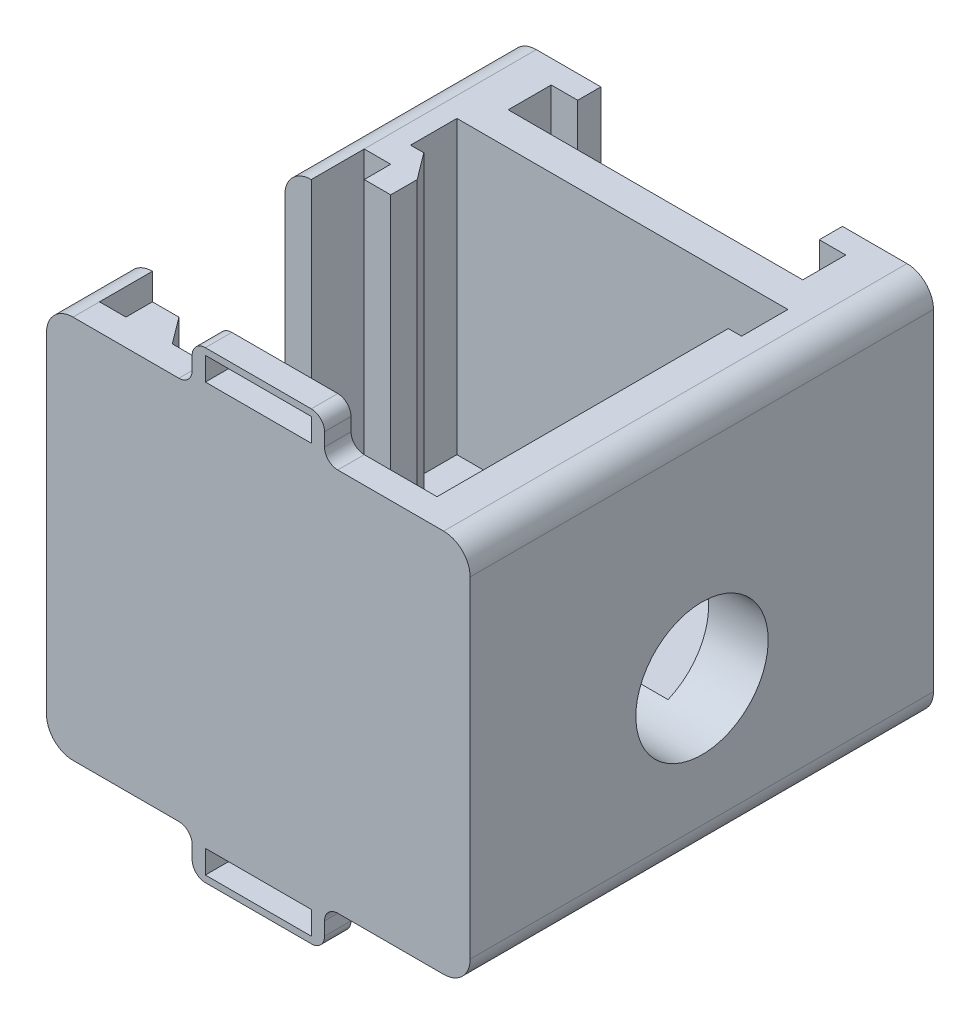
SolidWorks part; units mm, degrees
material "UNOBTANIUM"
ref_plane "Top Plane" through (0, 0, 0) normal (0, 0, 1) x (1, 0, 0)
ref_plane "Right Plane" through (0, 0, 0) normal (0, 1, 0) x (1, 0, 0)
ref_plane "Front Plane" through (0, 0, 0) normal (1, 0, 0) x (0, 0, -1)
ref_axis "x-axis" through (-17.6, 0, 0) along (1, 0, 0)
ref_axis "y-axis" through (0, -14.85, 0) along (0, 1, 0)
ref_axis "z-axis" through (0, 0, 36.75) along (0, 0, -1)
sketch "Sketch1" plane through (0, 0, 0) normal (0, 0, 1) x (1, 0, 0)
  line L1 (-16, 14.5) -> (16, 14.5)
  line L2 (-16, 14.5) -> (-16, -14.5)
  line L3 (-16, -14.5) -> (16, -14.5)
  line L4 (16, 14.5) -> (16, -14.5)
  line L5 (-16, 14.5) -> (16, -14.5) construction
  line L6 (-16, -14.5) -> (16, 14.5) construction
  point P0 (0, 0)
  dimension "D1" = 32
  dimension "D2" = 29
extrude "Boss-Extrude1" add sketch "Sketch1" along normal blind 35
fillet "Fillet1" radius 2 4 edges at (16, -14.5, 17.5) (16, 14.5, 17.5) (-16, -14.5, 17.5) (-16, 14.5, 17.5)
sketch "Sketch2" plane through (0, -14.5, 0) normal (0, -1, 0) x (1, 0, 0)
  line L0 (-9.125, 0) -> (-9.125, 1.75)
  line L1 (-14, 0) -> (14, 0) construction
  line L2 (-9.125, 1.75) -> (-11.125, 1.75)
  line L3 (-11.125, 1.75) -> (-11.125, 5)
  line L4 (-11.125, 5) -> (11.125, 5)
  line L5 (11.125, 5) -> (11.125, 1.75)
  line L6 (11.125, 1.75) -> (9.125, 1.75)
  line L7 (9.125, 1.75) -> (9.125, 0)
  line L9 (-9.125, 0) -> (9.125, 0)
  point P4 (0, 0)
  dimension "D1" = 18.25
  dimension "D2" = 1.75
  dimension "D3" = 3.25
  dimension "D4" = 22.25
extrude "Slot for Coil" cut sketch "Sketch2" against normal through all both and the other way through all
sketch "Sketch3" plane through (0, -14.5, 0) normal (0, -1, 0) x (1, 0, 0)
  line L0 (-9.125, 0) -> (-9.125, 1.75)
  line L1 (-9.125, 1.75) -> (-11.125, 1.75)
  line L2 (-11.125, 1.75) -> (-11.125, 5)
  line L3 (-11.125, 5) -> (11.125, 5)
  line L4 (11.125, 5) -> (11.125, 1.75)
  line L5 (11.125, 1.75) -> (9.125, 1.75)
  line L6 (9.125, 1.75) -> (9.125, 0)
  line L7 (9.125, 0) -> (-9.125, 0)
extrude "Boss-Extrude2" add sketch "Sketch3" against normal blind 7
sketch "Sketch4" plane through (0, 0, 1.75) normal (0, 0, -1) x (-1, 0, 0)
  line L1 (-9.125, 7.5) -> (-9.125, 6.5)
  line L2 (-9.125, 14.5) -> (-9.125, -7.5) construction
  arc A0 (-9.125, 7.5) -> (-9.125, 6.5) centre (-9.5, 7) cw
  dimension "D1" = 0.625
  dimension "D2" = 0.25
  dimension "D3" = 7
extrude "Boss-Extrude3" add sketch "Sketch4" along normal up to surface (1.75 mm away) up to face at (0, 1.1667, 0)
mirror "Mirror1" about plane through (0, 0, 0) normal (1, 0, 0) of "Boss-Extrude3"
sketch "Sketch5" plane through (0, 0, 0) normal (0, 0, -1) x (-1, 0, 0)
  line L0 (9.125, -7.5) -> (-9.125, -7.5) construction
  line L1 (-1, -7.5) -> (1, -7.5)
  line L2 (-1, -7.5) -> (-1, -14.5)
  line L3 (-1, -14.5) -> (1, -14.5)
  line L4 (1, -7.5) -> (1, -14.5)
  line L5 (14, -14.5) -> (-14, -14.5) construction
  point P8 (0, -7.5)
  dimension "D1" = 2
extrude "Cut-Extrude2" cut sketch "Sketch5" against normal offset from surface (33 mm away) 2 up to face at (0, 0, 35)
sketch "Sketch6" plane through (0, 14.5, 0) normal (0, 1, 0) x (1, 0, 0)
  line L0 (-12.5, -7.5) -> (-12.5, -11)
  line L1 (-12.5, -11) -> (-11.5, -11)
  line L2 (-11.5, -11) -> (-11.5, -33)
  line L3 (-11.5, -33) -> (11.5, -33)
  line L4 (11.5, -33) -> (11.5, -11)
  line L5 (11.5, -11) -> (12.5, -11)
  line L6 (12.5, -11) -> (12.5, -7.5)
  line L7 (12.5, -7.5) -> (-12.5, -7.5)
  line L8 (11.125, -5) -> (-11.125, -5) construction
  line L9 (0, -7.5) -> (0, -5) construction
  line L10 (14, -35) -> (-14, -35) construction
  dimension "D1" = 2.5
  dimension "D2" = 3.5
  dimension "D3" = 1
  dimension "D4" = 25
  dimension "D5" = 2
extrude "Cut-Extrude3" cut sketch "Sketch6" against normal up to surface (22 mm away) up to face at (7.0833, -7.5, 2.25)
sketch "Sketch7" plane through (0, -14.5, 0) normal (0, -1, 0) x (1, 0, 0)
  line L0 (1, 0) -> (14, 0) construction
  line L1 (1, 0) -> (-1, 0)
  line L2 (1, 0) -> (1, 33)
  line L3 (1, 33) -> (-1, 33)
  line L4 (-1, 0) -> (-1, 33)
  line L5 (1, 33) -> (1, 0) construction
extrude "Boss-Extrude4" add sketch "Sketch7" against normal blind 0.25
fillet "Fillet2" radius 6 1 edges at (0, -14.25, 33)
ref_axis "Axis1" through (63.07, 0, 17.75) along (-1, 0, 0)
ref_plane "Plane1" through (0, 0, 17.75) normal (0, 0, -1) x (-1, 0, 0)
sketch "Sketch9" plane through (0, 0, 17.75) normal (0, 0, -1) x (-1, 0, 0)
  line L0 (-15, 6) -> (-14, 6)
  line L1 (-16, -12.5) -> (-16, 12.5) construction
  line L2 (-14, 6) -> (-14, 3.325)
  line L3 (-14, 3.325) -> (-11.5, 3.325)
  line L4 (-11.5, 3.325) -> (-11.5, 0)
  line L5 (-63.07, 0) -> (46.93, 0) construction
  line L6 (-11.5, 0) -> (-16, 0)
  line L8 (-16, 0) -> (0, 0) construction
  line L9 (-11.5, -7.5) -> (-11.5, 14.5) construction
  line L10 (-15, 6) -> (-15, 5)
  line L11 (-15, 5) -> (-16, 5)
  line L12 (-16, 5) -> (-16, 0)
  dimension "D1" = 6.65
  dimension "D2" = 12
  dimension "D3" = 1
  dimension "D4" = 1
  dimension "D5" = 10
revolve "Cut-Revolve1" [suppressed] cut sketch "Sketch9" angle 360 about L8
sketch "Sketch10" plane through (0, 14.5, 0) normal (0, 1, 0) x (1, 0, 0)
  line L0 (11.5, -31) -> (13.5, -31)
  line L1 (11.5, -11) -> (11.5, -33) construction
  line L2 (13.5, -31) -> (13.5, -33)
  line L3 (13.5, -33) -> (11.5, -33)
  line L4 (11.5, -33) -> (11.5, -31)
  dimension "D1" = 2
  dimension "D2" = 2
extrude "Cut-Extrude4" [suppressed] cut sketch "Sketch10" against normal up to surface (20 mm away)
mirror "Mirror2" [suppressed] about plane through (0, 0, 0) normal (1, 0, 0)
sketch "Sketch11" plane through (-16, 0, 44) normal (1, 0, 0) x (0, 0, -1)
  line L0 (21, 25) -> (21, 0) construction
  line L4 (27, 25) -> (27, 0)
  line L5 (15, 25) -> (15, 0)
  line L6 (9, 12.5) -> (44, 12.5) construction
  line L7 (21, 0) -> (44, 0) construction
  line L8 (9, 12.5) -> (9, -12.5) construction
  arc A2 (27, 25) -> (15, 25) centre (21, 25) ccw
  arc A3 (15, 0) -> (27, 0) centre (21, 0) ccw
  point P2 (21, 12.5)
  dimension "D1" = 12
  dimension "D2" = 12
extrude "Cut-Extrude5" cut sketch "Sketch11" along normal up to surface (4.5 mm away) up to face at (-11.5, 3.5, 22)
sketch "Sketch14" plane through (0, 14.5, 0) normal (0, 1, 0) x (1, 0, 0)
  line L0 (-11.5, -11) -> (-11.5, -17) construction
  line L1 (-11.5, -13) -> (-14, -13)
  line L2 (-11.5, -13) -> (-11.5, -33)
  line L3 (-11.5, -33) -> (-14, -33)
  line L4 (-14, -13) -> (-14, -33)
  line L5 (-16, -35) -> (-16, -29) construction
  line L6 (-11.5, -29) -> (-11.5, -17) construction
  point P12 (-11.5, -23)
  dimension "D1" = 2
extrude "Cut-Extrude6" cut sketch "Sketch14" against normal up to surface (22 mm away) up to face at (-8.3333, -7.5, 17.1667)
sketch "Sketch16" plane through (0, 14.5, 0) normal (0, 1, 0) x (1, 0, 0)
  line L1 (-12, -13) -> (-10, -13)
  line L2 (-12, -13) -> (-12, -15)
  line L3 (-12, -15) -> (-10, -15)
  line L4 (-10, -13) -> (-10, -15)
  line L5 (-14, -33) -> (-14, -13) construction
  line L6 (-12, -33) -> (-12, -31)
  line L7 (-14, -33) -> (11.5, -33) construction
  line L8 (-12, -31) -> (-10, -31)
  line L9 (-10, -31) -> (-10, -33)
  line L10 (-10, -33) -> (-12, -33)
  line L11 (-12.5, -11) -> (-11.5, -11) construction
  line L13 (-11.5, -13) -> (-14, -13) construction
  line L14 (-14, -13) -> (-14, -17) construction
  dimension "D1" = 4
  dimension "D2" = 2
  dimension "D3" = 2
  dimension "D4" = 2
  dimension "D5" = 2
extrude "Boss-Extrude5" add sketch "Sketch16" against normal up to surface (22 mm away) up to face at (-9.75, -7.5, 16.125)
sketch "Sketch20" plane through (0, 14.5, 0) normal (0, 1, 0) x (1, 0, 0)
  line L0 (-11.5, -11) -> (-10, -13)
  line L1 (-10, -13) -> (-11.5, -13)
  line L2 (-11.5, -13) -> (-11.5, -11)
  line L3 (-10, -31) -> (-8.5, -33)
  line L4 (-1, -33) -> (-10, -33) construction
  line L5 (-8.5, -33) -> (-10, -33)
  line L6 (-10, -33) -> (-10, -31)
extrude "Boss-Extrude6" add sketch "Sketch20" against normal up to surface (22 mm away) up to face at (-10.375, -7.5, 19.5625)
sketch "Sketch21" plane through (0, 14.5, 0) normal (0, 1, 0) x (-1, 0, 0)
  line L0 (0, 0) -> (0, 35) construction
  line L1 (-14, 35) -> (14, 35) construction
  line L2 (8.5, 33) -> (-11.5, 33) construction
  line L3 (-5, 35) -> (5, 35)
  line L4 (-5, 35) -> (-5, 33)
  line L5 (-5, 33) -> (5, 33)
  line L6 (5, 35) -> (5, 33)
  point P12 (0, 35)
  dimension "D1" = 10
extrude "Boss-Extrude7" add sketch "Sketch21" along normal blind 3
sketch "Sketch23" plane through (0, 0, 35) normal (0, 0, 1) x (1, 0, 0)
  line L0 (0, 0) -> (0, 17.5) construction
  line L3 (-4, 17) -> (4, 17)
  line L4 (-4, 17) -> (-4, 15.25)
  line L5 (-4, 15.25) -> (4, 15.25)
  line L6 (4, 17) -> (4, 15.25)
  line L7 (-5, 17.5) -> (5, 17.5) construction
  point P3 (0, 17)
  dimension "D1" = 1.75
  dimension "D2" = 8
  dimension "D3" = 0.5
extrude "Cut-Extrude7" cut sketch "Sketch23" against normal up to next
mirror "Mirror3" about plane through (0, 0, 0) normal (0, 1, 0) of "Boss-Extrude7", "Cut-Extrude7"
fillet "Fillet3" radius 1 8 edges at (-5, 14.5, 34) (5, 14.5, 34) (5, 17.5, 34) (-5, 17.5, 34) (5, -14.5, 34) (-5, -14.5, 34) (5, -17.5, 34) (-5, -17.5, 34)
sketch "Sketch26" plane through (16, 0, 0) normal (1, 0, 0) x (0, 0, -1)
  circle A0 centre (-17.485, -2.89) radius 5
  dimension "D1" = 10
extrude "Cut-Extrude8" cut sketch "Sketch26" against normal up to next
